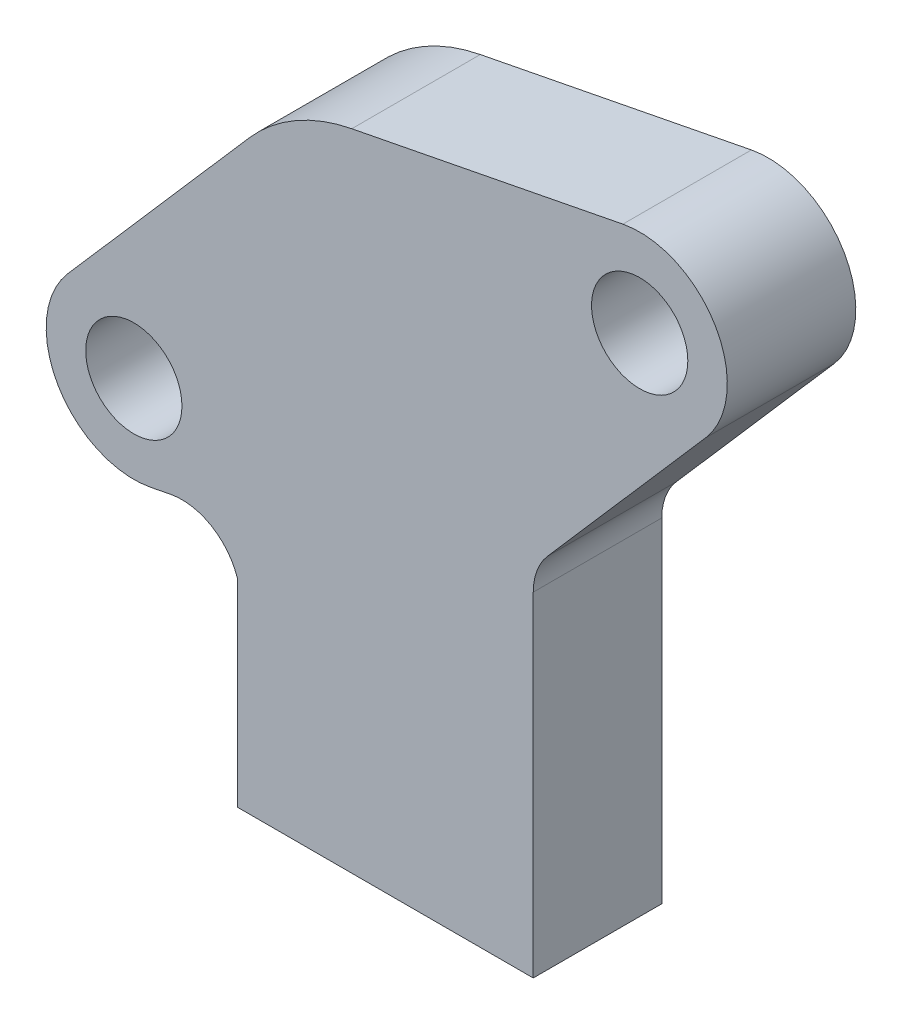
SolidWorks part; units mm, degrees
ref_plane "Front Plane" through (0, 0, 0) normal (0, 0, 1) x (1, 0, 0)
ref_plane "Top Plane" through (0, 0, 0) normal (0, 1, 0) x (1, 0, 0)
ref_plane "Right Plane" through (0, 0, 0) normal (1, 0, 0) x (0, 0, -1)
sketch "Sketch1" plane through (0, 0, 2.1073) normal (0, 0, 1) x (1, 0, 0)
  line L0 (13.3239, 2.6619) -> (0.6739, 2.6619) construction
  line L1 (0.6739, 2.6619) -> (0.6739, -2.4381) construction
  line L2 (0.6739, -2.4381) -> (13.3239, -2.4381) construction
  line L3 (13.3239, -2.4381) -> (13.3239, 2.6619) construction
  line L4 (13.6414, 2.9794) -> (0.3564, 2.9794)
  line L5 (0.3564, 2.9794) -> (0.3564, -2.7556)
  line L6 (0.3564, -2.7556) -> (13.6414, -2.7556)
  line L7 (15.111, -5.1606) -> (15.111, 13.0027)
  line L8 (15.8915, 15.0877) -> (24.488, 24.9606)
  line L9 (19.9838, 32.7623) -> (5.2476, 29.8855)
  line L10 (-0.3323, 26.6639) -> (-10.1918, 15.3404)
  line L11 (-5.6875, 7.5388) -> (-4.5981, 7.7515)
  line L12 (-0.9761, 5.6344) -> (-0.9761, -5.1606)
  line L13 (-0.9761, -5.1606) -> (15.111, -5.1606)
  line L14 (15.111, -5.1606) -> (15.111, 13.0027)
  line L15 (15.8915, 15.0877) -> (24.488, 24.9606)
  line L16 (19.9838, 32.7623) -> (5.2476, 29.8855)
  line L17 (-0.3323, 26.6639) -> (-10.1918, 15.3404)
  line L18 (-5.6875, 7.5388) -> (-4.5981, 7.7515)
  line L19 (-0.9761, 5.6344) -> (-0.9761, -5.1606)
  line L20 (-0.9761, -5.1606) -> (15.111, -5.1606)
  line L21 (13.6414, -2.7556) -> (13.6414, 2.9794)
  circle A0 centre (-6.6, 12.213) radius 2.6162 construction
  circle A1 centre (20.8963, 28.088) radius 2.6162 construction
  circle A2 centre (-6.6, 12.213) radius 2.6162
  circle A3 centre (20.8963, 28.088) radius 2.6162
  arc A5 (15.8915, 15.0877) -> (15.111, 13.0027) centre (18.286, 13.0027) ccw
  arc A6 (24.488, 24.9606) -> (19.9838, 32.7623) centre (20.8963, 28.088) ccw
  arc A7 (5.2476, 29.8855) -> (-0.3323, 26.6639) centre (7.1481, 20.1505) ccw
  arc A8 (-10.1918, 15.3404) -> (-5.6875, 7.5388) centre (-6.6, 12.213) ccw
  arc A9 (-0.9761, 5.6344) -> (-4.5981, 7.7515) centre (-3.9898, 4.6353) ccw
  arc A10 (15.8915, 15.0877) -> (15.111, 13.0027) centre (18.286, 13.0027) ccw
  arc A11 (24.488, 24.9606) -> (19.9838, 32.7623) centre (20.8963, 28.088) ccw
  arc A12 (5.2476, 29.8855) -> (-0.3323, 26.6639) centre (7.1481, 20.1505) ccw
  arc A13 (-10.1918, 15.3404) -> (-5.6875, 7.5388) centre (-6.6, 12.213) ccw
  arc A14 (-0.9761, 5.6344) -> (-4.5981, 7.7515) centre (-3.9898, 4.6353) ccw
  line M17 (13.841, -3.7636) -> (0.2939, -3.7636)
  line M18 (0.2939, -3.7636) -> (0.2939, 9.933)
  arc M19 (0.2939, 9.933) -> (-0.8698, 15.2437) centre (-12.4061, 9.933) ccw
  line M20 (-0.8698, 15.2437) -> (-0.9761, 15.4746)
  arc M21 (-0.9761, 15.4746) -> (15.111, 16.1833) centre (6.9229, 19.1109) cw
  line M22 (15.111, 16.1833) -> (14.5824, 14.7049)
  arc M23 (14.5824, 14.7049) -> (13.841, 10.4291) centre (26.541, 10.4291) ccw
  line M24 (13.841, 10.4291) -> (13.841, -3.7636)
  line M25 (15.111, -5.1606) -> (15.111, 13.0027)
  arc M26 (15.111, 13.0027) -> (15.8915, 15.0877) centre (18.286, 13.0027) cw
  line M27 (15.8915, 15.0877) -> (24.488, 24.9606)
  arc M28 (24.488, 24.9606) -> (19.9838, 32.7623) centre (20.8963, 28.088) ccw
  line M29 (19.9838, 32.7623) -> (5.2476, 29.8855)
  arc M30 (5.2476, 29.8855) -> (-0.3323, 26.6639) centre (7.1481, 20.1505) ccw
  line M31 (-0.3323, 26.6639) -> (-10.1918, 15.3404)
  arc M32 (-10.1918, 15.3404) -> (-5.6875, 7.5388) centre (-6.6, 12.213) ccw
  line M33 (-5.6875, 7.5388) -> (-4.5981, 7.7515)
  arc M34 (-4.5981, 7.7515) -> (-0.9761, 5.6344) centre (-3.9898, 4.6353) cw
  line M35 (-0.9761, 5.6344) -> (-0.9761, -5.1606)
  line M36 (-0.9761, -5.1606) -> (15.111, -5.1606)
  circle M37 centre (20.8963, 28.088) radius 2.6162
  circle M38 centre (-6.6, 12.213) radius 2.6162
  dimension "D1" = 0
  dimension "D2" = 0.3175
extrude "Boss-Extrude1" add sketch "Sketch1" along normal blind 6.985 contours M36 M25 M26 M27 M28 M29 M30 M31 M32 M33 M34 M35 M37 M38 M24 M17 M18 M19 M20 M21 M22 M23 region at (7.0675, -4.63, 2.1073)
sketch "Sketch2" plane through (0, 0, 9.0923) normal (0, 0, 1) x (1, 0, 0)
  line L0 (0.2939, 2.9794) -> (13.841, 2.9794)
  line L1 (0.6739, 2.6619) -> (13.3239, 2.6619) construction
  line L5 (13.841, -3.7636) -> (13.841, 10.4291)
  line L6 (0.2939, -3.7636) -> (13.841, -3.7636)
  line L7 (0.2939, 9.933) -> (0.2939, -3.7636)
  line L8 (-0.9761, 15.4746) -> (-0.8698, 15.2437)
  line L9 (14.5824, 14.7049) -> (15.111, 16.1833)
  line L10 (13.841, 2.9794) -> (13.841, 10.4291)
  line L12 (0.2939, 9.933) -> (0.2939, 2.9794)
  line L13 (-0.9761, 15.4746) -> (-0.8698, 15.2437)
  line L14 (14.5824, 14.7049) -> (15.111, 16.1833)
  arc A3 (0.2939, 9.933) -> (-0.8698, 15.2437) centre (-12.4061, 9.933) ccw
  arc A4 (15.111, 16.1833) -> (-0.9761, 15.4746) centre (6.9229, 19.1109) ccw
  arc A5 (14.5824, 14.7049) -> (13.841, 10.4291) centre (26.541, 10.4291) ccw
  arc A6 (0.2939, 9.933) -> (-0.8698, 15.2437) centre (-12.4061, 9.933) ccw
  arc A7 (15.111, 16.1833) -> (-0.9761, 15.4746) centre (6.9229, 19.1109) ccw
  arc A8 (14.5824, 14.7049) -> (13.841, 10.4291) centre (26.541, 10.4291) ccw
  dimension "D2" = 0.3175
  dimension "D1" = 0
extrude "Boss-Extrude2" add sketch "Sketch2" against normal blind 6.0325
sketch "Sketch3" plane through (0, -5.1606, 0) normal (0, -1, 0) x (1, 0, 0)
  line L2 (-0.9761, 2.1073) -> (15.111, 2.1073) construction
  line L3 (3.8925, 7.8223) -> (10.2425, 7.8223)
  line L4 (3.8925, 7.8223) -> (3.8925, -3.6077)
  line L5 (3.8925, -3.6077) -> (10.2425, -3.6077)
  line L6 (10.2425, 7.8223) -> (10.2425, -3.6077)
  line L7 (3.8925, 7.8223) -> (10.2425, -3.6077) construction
  line L8 (3.8925, -3.6077) -> (10.2425, 7.8223) construction
  point P0 (7.0675, 2.1073)
  dimension "D2" = 5.715
  dimension "D1" = 6.35
extrude "Cut-Extrude1" cut sketch "Sketch3" against normal blind 1.524 and the other way through all
sketch "Sketch4" plane through (0, 0, 9.0923) normal (0, 0, 1) x (1, 0, 0)
  line L4 (13.841, 2.9794) -> (0.2939, 2.9794)
  line L5 (13.841, -3.7636) -> (13.841, 2.9794)
  line L6 (0.2939, -3.7636) -> (13.841, -3.7636)
  line L7 (0.2939, 2.9794) -> (0.2939, -3.7636)
  line L8 (13.841, 2.9794) -> (0.2939, 2.9794)
  line L9 (13.841, -3.7636) -> (13.841, 2.9794)
  line L10 (0.2939, -3.7636) -> (13.841, -3.7636)
  line L11 (0.2939, 2.9794) -> (0.2939, -3.7636)
  dimension "D1" = 0
extrude "Boss-Extrude3" add sketch "Sketch4" against normal up to surface (1.27 mm away) up to face at (7.0675, -4.4621, 7.8223)
